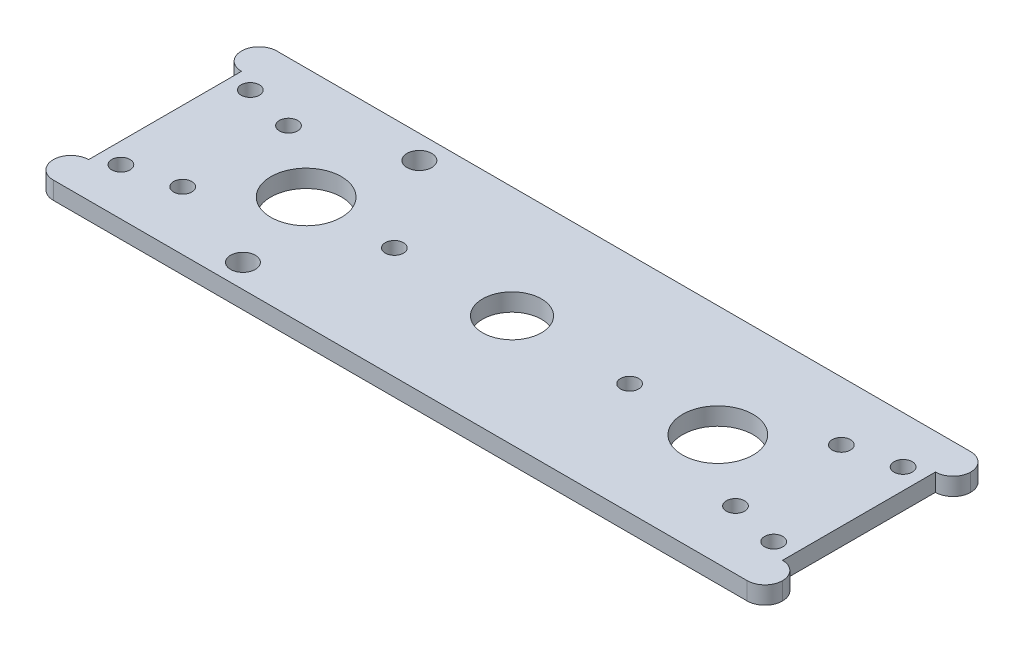
SolidWorks part; units mm, degrees
material "Thornel Mat VMA"
ref_plane "Front Plane" through (0, 0, 0) normal (0, 0, 1) x (1, 0, 0)
ref_plane "Top Plane" through (0, 0, 0) normal (0, 1, 0) x (1, 0, 0)
ref_plane "Right Plane" through (0, 0, 0) normal (1, 0, 0) x (0, 0, -1)
sketch "Sketch1" plane through (0, 0, 0) normal (0, 1, 0) x (1, 0, 0)
  line L0 (0, 0) -> (0, 56.5511) construction
  line L1 (0, 0) -> (118.6796, 0) construction
  line L2 (-62, 19) -> (62, 19)
  line L5 (-62, -19) -> (62, -19)
  line L6 (62, 19) -> (62, 13)
  line L7 (62, 13) -> (59, 13)
  line L8 (59, 13) -> (59, -13)
  line L9 (62, -13) -> (59, -13)
  line L10 (62, -19) -> (62, -13)
  line L11 (-62, -19) -> (-62, -13)
  line L12 (-62, -13) -> (-59, -13)
  line L13 (-59, 13) -> (-59, -13)
  line L14 (-62, 13) -> (-59, 13)
  line L15 (-62, 19) -> (-62, 13)
  circle A0 centre (55.5, 11) radius 1.55
  circle A1 centre (-55.5, 11) radius 1.55
  circle A2 centre (-55.5, -11) radius 1.55
  circle A3 centre (55.5, -11) radius 1.55
  circle A4 centre (0, 0) radius 5
  circle A5 centre (20, 0) radius 1.55
  circle A6 centre (-20, 0) radius 1.55
  circle A7 centre (35, 0) radius 6
  circle A8 centre (-35, 0) radius 6
  circle A9 centre (47, 9) radius 1.55
  circle A10 centre (47, -9) radius 1.55
  circle A11 centre (-47, -9) radius 1.55
  circle A12 centre (-47, 9) radius 1.55
  point P13 (0, 19)
  point P18 (-61, 0)
  point P19 (61, 0)
  point P28 (59, 0)
  dimension "D1" = 3.1
  dimension "D2" = 3.5
  dimension "D3" = 8
  dimension "D4" = 3.1
  dimension "D5" = 10
  dimension "D6" = 20
  dimension "D11" = 35
  dimension "D12" = 12
  dimension "D13" = 8.5
  dimension "D14" = 2
  dimension "D7" = 38
  dimension "D8" = 124
  dimension "D9" = 3
  dimension "D10" = 6
extrude "Boss-Extrude1" add sketch "Sketch1" along normal blind 3
fillet "Fillet1" radius 3 8 edges at (-62, 1.5, -19) (-62, 1.5, -13) (-62, 1.5, 13) (-62, 1.5, 19) (62, 1.5, 19) (62, 1.5, 13) (62, 1.5, -13) (62, 1.5, -19)
sketch "草图2" plane through (0, 3, 0) normal (0, 1, 0) x (1, 0, 0)
  line L0 (0, 19) -> (0, -19) construction
  line L1 (59, 19) -> (-59, 19) construction
  line L2 (-59, -19) -> (59, -19) construction
  line L3 (0, 0) -> (-21.55, 0) construction
  circle A0 centre (-20, 0) radius 1.55 construction
sketch "草图3" plane through (0, 0, 0) normal (0, -1, 0) x (1, 0, 0)
  circle A0 centre (-30.75, -15) radius 2.1 construction
  circle A1 centre (-30.75, -15) radius 2.1
  circle A2 centre (-30.75, 15) radius 2.1 construction
  circle A3 centre (-30.75, 15) radius 2.1
extrude "切除-拉伸1" cut sketch "草图3" against normal blind 10
